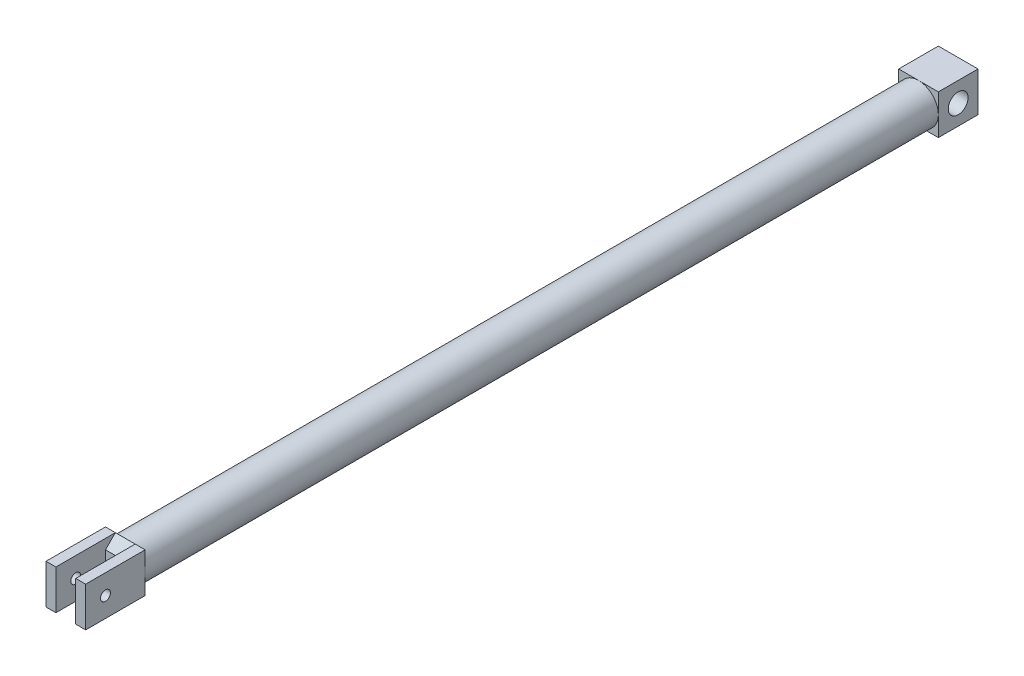
SolidWorks part; units mm, degrees
ref_plane "Ebene vorne" through (0, 0, 0) normal (0, 0, 1) x (1, 0, 0)
ref_plane "Ebene oben" through (0, 0, 0) normal (0, 1, 0) x (1, 0, 0)
ref_plane "Ebene rechts" through (0, 0, 0) normal (1, 0, 0) x (0, 0, -1)
sketch "Skizze1" plane through (0, 0, 0) normal (0, 0, 1) x (1, 0, 0)
  circle A0 centre (0, 0) radius 10
  dimension "D1" = 20
extrude "Aufsatz-Linear austragen1" add sketch "Skizze1" along normal blind 400
sketch "Skizze2" plane through (0, 0, 0) normal (0, 0, -1) x (-1, 0, 0)
  line L1 (-10, 10) -> (10, 10)
  line L2 (-10, 10) -> (-10, -10)
  line L3 (-10, -10) -> (10, -10)
  line L4 (10, 10) -> (10, -10)
  line L5 (-10, 10) -> (10, -10) construction
  line L6 (-10, -10) -> (10, 10) construction
  point P0 (0, 0)
  dimension "D1" = 20
  dimension "D2" = 20
extrude "Aufsatz-Linear austragen2" add sketch "Skizze2" along normal blind 20
sketch "Skizze3" plane through (10, 0, 0) normal (1, 0, 0) x (0, 0, -1)
  line L0 (20, 10) -> (0, 10) construction
  line L1 (20, 10) -> (20, -10) construction
  circle A0 centre (10, 0) radius 5
  dimension "D1" = 10
  dimension "D2" = 10
  dimension "D3" = 10
extrude "Schnitt-Linear austragen1" cut sketch "Skizze3" against normal blind 30
sketch "Skizze4" plane through (0, 0, 400) normal (0, 0, 1) x (1, 0, 0)
  line L1 (-10, 10) -> (10, 10)
  line L2 (-10, 10) -> (-10, -10)
  line L3 (-10, -10) -> (10, -10)
  line L4 (10, 10) -> (10, -10)
  line L5 (-10, 10) -> (10, -10) construction
  line L6 (-10, -10) -> (10, 10) construction
  point P0 (0, 0)
extrude "Aufsatz-Linear austragen3" add sketch "Skizze4" along normal blind 30
sketch "Skizze5" plane through (0, 0, 430) normal (0, 0, 1) x (1, 0, 0)
  line L0 (-10, -10) -> (10, -10) construction
  line L1 (-5, 10) -> (5, 10)
  line L2 (-5, 10) -> (-5, -10)
  line L3 (-5, -10) -> (5, -10)
  line L4 (5, 10) -> (5, -10)
  line L5 (-5, 10) -> (5, -10) construction
  line L6 (-5, -10) -> (5, 10) construction
  point P0 (0, 0)
  dimension "D1" = 10
extrude "Schnitt-Linear austragen2" cut sketch "Skizze5" against normal blind 25
chamfer "Fase1" distance 5 angle 45 2 edges at (0, -10, 405) (0, 10, 405)
sketch "Skizze6" plane through (10, 0, 0) normal (1, 0, 0) x (0, 0, -1)
  line L0 (-430, 0) -> (-318.8256, 0) construction
  line L1 (-430, -10) -> (-430, 10) construction
  circle A0 centre (-420, 0) radius 2.5
  dimension "D2" = 5
  dimension "D1" = 10
extrude "Schnitt-Linear austragen3" cut sketch "Skizze6" against normal blind 25
